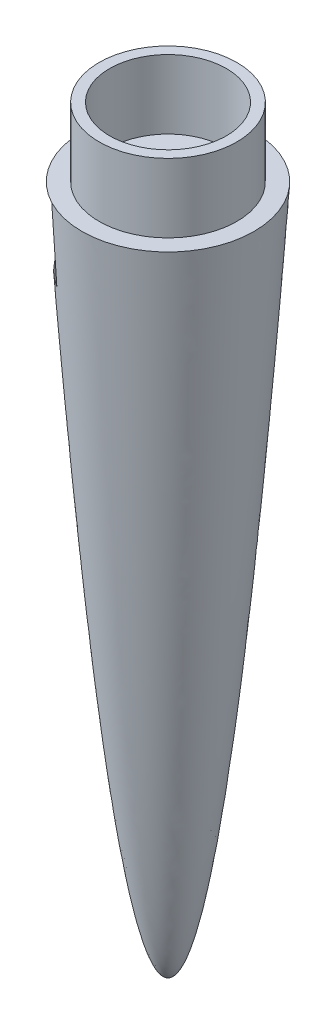
SolidWorks part; units mm, degrees
ref_plane "Front Plane" through (0, 0, 0) normal (0, 0, 1) x (1, 0, 0)
ref_plane "Top Plane" through (0, 0, 0) normal (0, 1, 0) x (1, 0, 0)
ref_plane "Right Plane" through (0, 0, 0) normal (1, 0, 0) x (0, 0, -1)
sketch "Sketch4" plane through (0, 0, 0) normal (1, 0, 0) x (0, 0, -1)
  line L2 (0, 0) -> (0, 76.2113) construction
  line L4 (-7.9376, 63.4611) -> (-6.35, 63.4611)
  line L5 (0, 63.4611) -> (0, 0)
  line L7 (-6.35, 63.4611) -> (-6.35, 69.8111)
  line L8 (-6.35, 69.8111) -> (-5.3823, 69.8111)
  line L9 (-5.3823, 63.4611) -> (-5.3823, 69.8111)
  line L10 (-5.3823, 63.4611) -> (0, 63.4611)
  spline S2 degree 4 poles (0, 0) (-0.0369, -0.0001) (-0.0857, 0.0049) (-0.1472, 0.0201) (-0.2239, 0.0521) (-0.2835, 0.0844) (-0.3519, 0.1307) (-0.4322, 0.1981) (-0.5281, 0.2957) (-0.6496, 0.4473) (-0.8101, 0.6931) (-1.0368, 1.1292) (-1.3777, 1.9711) (-1.8936, 3.6858) (-2.5213, 6.549) (-3.1805, 10.4791) (-3.8279, 15.203) (-4.4238, 20.2846) (-4.952, 25.3273) (-5.438, 30.4468) (-5.8804, 35.453) (-6.3066, 40.6522) (-6.6888, 45.5403) (-7.0847, 50.9452) (-7.4083, 55.4998) (-7.7709, 60.8988) (-7.9755, 64.0296) (-8.152, 66.797) (-8.2847, 68.8901) (-8.3035, 69.2115) (-8.3458, 69.8785) knots 0 0 0 0 0 0.00207 0.002771 0.003558 0.00469 0.005895 0.007433 0.009472 0.012413 0.016849 0.024014 0.037179 0.063737 0.117806 0.189835 0.261865 0.333894 0.405923 0.477952 0.549982 0.622011 0.69404 0.766069 0.838098 0.910128 0.955064 0.977532 1 1 1 1 1 construction
  spline S3 degree 4 poles (0, 0) (-0.0369, -0.0001) (-0.0857, 0.0049) (-0.1472, 0.0201) (-0.2239, 0.0521) (-0.2835, 0.0844) (-0.3519, 0.1307) (-0.4322, 0.1981) (-0.5281, 0.2957) (-0.6496, 0.4473) (-0.8101, 0.6931) (-1.0368, 1.1292) (-1.3777, 1.9711) (-1.8936, 3.6858) (-2.5213, 6.549) (-3.1805, 10.4791) (-3.8279, 15.203) (-4.4238, 20.2846) (-4.952, 25.3273) (-5.438, 30.4468) (-5.8804, 35.453) (-6.3066, 40.6522) (-6.6888, 45.5403) (-7.0847, 50.9452) (-7.4083, 55.4998) (-7.7085, 59.9694) (-7.8623, 62.3036) (-7.9376, 63.4611) knots 0 0 0 0 0 0.00207 0.002771 0.003558 0.00469 0.005895 0.007433 0.009472 0.012413 0.016849 0.024014 0.037179 0.063737 0.117806 0.189835 0.261865 0.333894 0.405923 0.477952 0.549982 0.622011 0.69404 0.766069 0.838098 0.910128 0.910128 0.910128 0.910128 0.910128
  dimension "D1" = 0.9677
  dimension "D2" = 7.9376
  dimension "D3" = 63.4611
  dimension "D4" = 6.35
revolve "Revolve2" add sketch "Sketch4" angle 360 about L2
